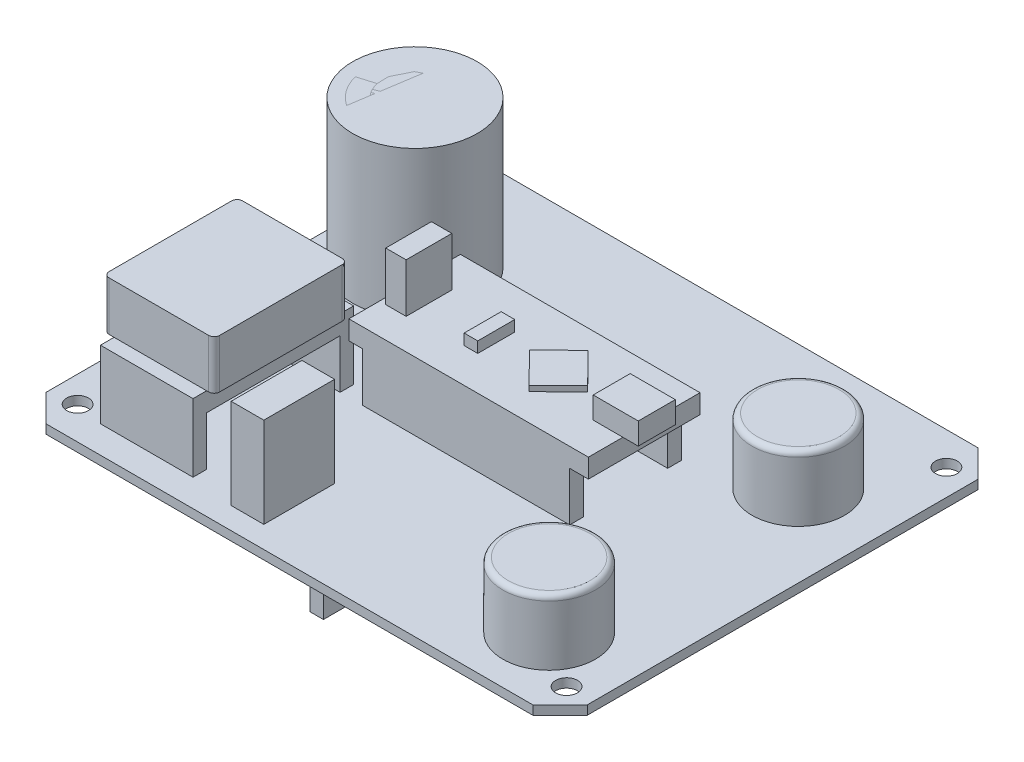
SolidWorks part; units mm, degrees
ref_plane "前视基准面" through (0, 0, 0) normal (0, 0, 1) x (1, 0, 0)
ref_plane "上视基准面" through (0, 0, 0) normal (0, 1, 0) x (1, 0, 0)
ref_plane "右视基准面" through (0, 0, 0) normal (1, 0, 0) x (0, 0, -1)
sketch "草图1" plane through (0, 0, 0) normal (0, 1, 0) x (1, 0, 0)
  line L0 (-49.7, 35.88) -> (-44.7, 40.88)
  line L1 (-44.7, 40.88) -> (44.7, 40.88)
  line L2 (-49.7, 35.88) -> (-49.7, -35.88)
  line L3 (-44.7, -40.88) -> (44.7, -40.88)
  line L4 (49.7, 35.88) -> (49.7, -35.88)
  line L5 (-49.7, 40.88) -> (-46.9566, 38.6234) construction
  line L6 (-49.7, -40.88) -> (-46.9566, -38.6234) construction
  line L7 (44.7, 40.88) -> (49.7, 35.88)
  line L8 (44.7, -40.88) -> (49.7, -35.88)
  line L9 (-49.7, -35.88) -> (-44.7, -40.88)
  line L10 (46.9566, 38.6234) -> (49.7, 40.88) construction
  line L11 (46.9566, -38.6234) -> (49.7, -40.88) construction
  line L12 (0, 0) -> (0, 46.3882) construction
  line L13 (0, 0) -> (77.8977, 0) construction
  line L14 (-39.7, -6.38) -> (-22.7, -6.38)
  line L15 (-39.7, -33.38) -> (-22.7, -33.38)
  line L16 (-39.7, -33.38) -> (-39.7, -35.88)
  line L17 (-39.7, -35.88) -> (-22.7, -35.88)
  line L18 (-22.7, -33.38) -> (-22.7, -35.88)
  line L19 (-39.7, -8.88) -> (-22.7, -8.88)
  line L20 (-39.7, -6.38) -> (-39.7, -8.88)
  line L21 (-22.7, -6.38) -> (-22.7, -8.88)
  line L22 (-18.5299, 11.62) -> (19.4701, 11.62)
  line L23 (-14.7, -23.88) -> (-8.7, -23.88)
  line L24 (-14.7, -23.88) -> (-14.7, -36.88)
  line L25 (-14.7, -36.88) -> (-8.7, -36.88)
  line L26 (-8.7, -23.88) -> (-8.7, -36.88)
  line L27 (-18.5299, -6.38) -> (19.4701, -6.38)
  line L28 (-18.5299, -6.38) -> (-18.5299, -8.88)
  line L29 (-18.5299, -8.88) -> (19.4701, -8.88)
  line L30 (19.4701, -6.38) -> (19.4701, -8.88)
  line L31 (-18.5299, 9.12) -> (19.4701, 9.12)
  line L32 (-18.5299, 11.62) -> (-18.5299, 9.12)
  line L33 (19.4701, 11.62) -> (19.4701, 9.12)
  circle A0 centre (-44.9, 34.88) radius 2
  circle A1 centre (44.9, 34.88) radius 2
  circle A2 centre (44.9, -34.88) radius 2
  circle A3 centre (-44.9, -34.88) radius 2
  circle A4 centre (-35.7, 17.88) radius 11.44
  circle A5 centre (34.7, 17.88) radius 8.5
  circle A6 centre (34.7, -27.88) radius 8.5
  point P0 (0, 0)
  dimension "D11" = 4
  dimension "D12" = 6
  dimension "D13" = 4.8
  dimension "D14" = 22.88
  dimension "D15" = 14
  dimension "D16" = 23
  dimension "D17" = 15
  dimension "D18" = 13
  dimension "D1" = 81.76
  dimension "D2" = 99.4
  dimension "D3" = 5
  dimension "D4" = 45
  dimension "D5" = 5
  dimension "D6" = 45
  dimension "D7" = 5
  dimension "D8" = 45
  dimension "D9" = 5
  dimension "D10" = 45
  dimension "D19" = 17
  dimension "D20" = 2.5
  dimension "D22" = 6
  dimension "D23" = 13
  dimension "D24" = 4
  dimension "D25" = 8
  dimension "D26" = 10
  dimension "D27" = 5
  dimension "D28" = 38
  dimension "D21" = 2
  dimension "D29" = 2
extrude "凸台-拉伸1" add sketch "草图1" against normal blind 1.66 contours A0 | L2 L9 L3 L8 L4 L7 L1 L0 | A1 | A3 | A2 region at (-44.9, 0, -34.88)
extrude "凸台-拉伸2" add sketch "草图1<3>" along normal blind 9 contours L30 L27 L28 L29 | L18 L15 L16 L17 | L31 L33 L22 L32 | L14 L21 L19 L20 region at (-31.2, 0, 34.63) region at (0.4701, 0, 7.63)
sketch "草图1<3>" plane through (0, 0, 0) normal (0, 1, 0) x (1, 0, 0) same geometry as "草图1"
extrude "凸台-拉伸3" add sketch "草图1<4>" along normal blind 16.58 contours L23 L26 L25 L24
sketch "草图1<4>" plane through (0, 0, 0) normal (0, 1, 0) x (1, 0, 0) same geometry as "草图1"
sketch "草图2" plane through (0, 0, 0) normal (0, 1, 0) x (1, 0, 0)
  circle A0 centre (-35.7, 17.88) radius 9.0479
  circle A1 centre (-35.7, 17.88) radius 5.836
extrude "凸台-拉伸4" add sketch "草图2" along normal blind 27 contours A1 | A0 region at (-35.7, 0, -17.88)
extrude "凸台-拉伸6" add sketch "草图2<4>" along normal blind 27 separate body contours A1
sketch "草图2<4>" plane through (0, 0, 0) normal (0, 1, 0) x (1, 0, 0) same geometry as "草图2"
extrude "凸台-拉伸7" add sketch "草图1<5>" along normal blind 27 separate body contours A4
sketch "草图1<5>" plane through (0, 0, 0) normal (0, 1, 0) x (1, 0, 0) same geometry as "草图1"
extrude "凸台-拉伸8" add sketch "草图1<6>" along normal blind 12 contours A5
sketch "草图1<6>" plane through (0, 0, 0) normal (0, 1, 0) x (1, 0, 0) same geometry as "草图1"
fillet "圆角1" radius 1 1 edges at (34.7, 12, -9.38)
extrude "凸台-拉伸9" add sketch "草图1<7>" along normal blind 12 contours A6
sketch "草图1<7>" plane through (0, 0, 0) normal (0, 1, 0) x (1, 0, 0) same geometry as "草图1"
fillet "圆角2" radius 1 1 edges at (34.7, 12, 36.38)
sketch "草图4" plane through (0, -1.66, 0) normal (0, -1, 0) x (1, 0, 0)
  line L0 (0, 43.8226) -> (0, -47.1107) construction
  line L1 (-44.7, 40.88) -> (44.7, 40.88) construction
  line L2 (-16, 19.88) -> (16, 19.88)
  line L3 (-16, 19.88) -> (-16, 17.38)
  line L4 (-16, 17.38) -> (16, 17.38)
  line L5 (16, 19.88) -> (16, 17.38)
  line L6 (-16, 19.88) -> (16, 17.38) construction
  line L7 (-16, 17.38) -> (16, 19.88) construction
  line L8 (-16, -21.12) -> (16, -21.12)
  line L9 (-16, -18.62) -> (16, -18.62)
  line L10 (-16, -18.62) -> (-16, -21.12)
  line L11 (16, -18.62) -> (16, -21.12)
  line L12 (-44.7, -40.88) -> (44.7, -40.88) construction
  line L13 (-1.25, 35.88) -> (1.25, 35.88)
  line L14 (-1.25, 35.88) -> (-1.25, 21.88)
  line L15 (-1.25, 21.88) -> (1.25, 21.88)
  line L16 (1.25, 35.88) -> (1.25, 21.88)
  line L17 (-1.25, 35.88) -> (1.25, 21.88) construction
  line L18 (-1.25, 21.88) -> (1.25, 35.88) construction
  line L19 (-27, -25.88) -> (-18, -25.88)
  line L20 (-27, -25.88) -> (-27, -37.88)
  line L21 (-27, -37.88) -> (-18, -37.88)
  line L22 (-18, -25.88) -> (-18, -37.88)
  line L23 (-27, -25.88) -> (-18, -37.88) construction
  line L24 (-27, -37.88) -> (-18, -25.88) construction
  line L25 (-27, -23.88) -> (-18, -23.88)
  line L26 (-27, -23.88) -> (-27, -25.88)
  line L27 (-27, -25.88) -> (-18, -25.88)
  line L28 (-18, -23.88) -> (-18, -25.88)
  line L29 (-27, -23.88) -> (-18, -25.88) construction
  line L30 (-27, -25.88) -> (-18, -23.88) construction
  line L31 (27, -25.88) -> (18, -25.88)
  line L32 (18, -23.88) -> (18, -25.88)
  line L33 (27, -23.88) -> (18, -23.88)
  line L34 (27, -23.88) -> (27, -25.88)
  line L35 (27, -37.88) -> (18, -37.88)
  line L36 (18, -25.88) -> (18, -37.88)
  line L37 (27, -25.88) -> (18, -25.88)
  line L38 (27, -25.88) -> (27, -37.88)
  point P3 (0, 18.63)
  point P11 (0, 28.88)
  point P19 (-22.5, -31.88)
  point P24 (-22.5, -24.88)
  point P29 (-16, -19.87)
  point P36 (0, 0)
  dimension "D1" = 2.5
  dimension "D2" = 32
  dimension "D3" = 21
  dimension "D5" = 2.5
  dimension "D6" = 14
  dimension "D7" = 5
  dimension "D8" = 9
  dimension "D9" = 3
  dimension "D10" = 2
  dimension "D11" = 12
  dimension "D12" = 2
  dimension "D4" = 2
extrude "凸台-拉伸10" add sketch "草图4" along normal blind 9 contours L16 L13 L14 L15 | L9 L11 L8 L10 | L4 L5 L2 L3 region at (0, -1.66, 28.88)
extrude "凸台-拉伸11" add sketch "草图4<5>" along normal blind 11 contours L22 L19 L20 L21 | L38 L31 L36 L35 region at (-22.5, -1.66, -31.88) region at (22.5, -1.66, -31.88)
sketch "草图4<5>" plane through (0, -1.66, 0) normal (0, -1, 0) x (1, 0, 0) same geometry as "草图4"
fillet "圆角4" radius 4.5 4 edges at (27, -12.66, -31.88) (18, -12.66, -31.88) (-18, -12.66, -31.88) (-27, -12.66, -31.88)
extrude "凸台-拉伸12" add sketch "草图4<6>" along normal blind 11 separate body contours L28 L25 L26 L19 | L34 L33 L32 L31 region at (-22.5, -1.66, -24.88) region at (22.5, -1.66, -24.88)
sketch "草图4<6>" plane through (0, -1.66, 0) normal (0, -1, 0) x (1, 0, 0) same geometry as "草图4"
sketch "草图5" plane through (0, 0, -23.88) normal (0, 0, 1) x (1, 0, 0)
  circle A0 centre (-22.5, -7.16) radius 3
  circle A1 centre (22.5, -7.16) radius 3
extrude "切除-拉伸1" cut sketch "草图5" against normal blind 11
sketch "草图6" plane through (0, 0, -34.88) normal (0, 0, 1) x (1, 0, 0)
  circle A0 centre (-22.5, -7.16) radius 1
  circle A1 centre (22.5, -7.16) radius 1
extrude "凸台-拉伸13" add sketch "草图6" along normal blind 8
sketch "草图7" plane through (0, 9, 0) normal (0, 1, 0) x (1, 0, 0)
  line L1 (-21.0893, 11.62) -> (22.9107, 11.62)
  line L2 (-21.0893, 11.62) -> (-21.0893, -8.88)
  line L3 (-21.0893, -8.88) -> (22.9107, -8.88)
  line L4 (22.9107, 11.62) -> (22.9107, -8.88)
  line L5 (-39.7, -6.38) -> (-22.7, -6.38)
  line L6 (-39.7, -6.38) -> (-39.7, -35.88)
  line L7 (-39.7, -35.88) -> (-22.7, -35.88)
  line L8 (-22.7, -6.38) -> (-22.7, -35.88)
  dimension "D1" = 44
extrude "凸台-拉伸14" add sketch "草图7" along normal blind 3.5
sketch "草图8" plane through (0, 12.5, 0) normal (0, 1, 0) x (1, 0, 0)
  line L0 (1.474, 1.7574) -> (6.9164, 7.0865)
  line L1 (1.474, 1.7574) -> (7.0356, -3.9225)
  line L2 (6.9164, 7.0865) -> (12.478, 1.4065)
  line L3 (7.0356, -3.9225) -> (12.478, 1.4065)
  line L5 (17.461, 4.2465) -> (25.738, 4.2465)
  line L6 (17.461, 4.2465) -> (17.461, -2.5511)
  line L7 (17.461, -2.5511) -> (25.738, -2.5511)
  line L8 (25.738, 4.2465) -> (25.738, -2.5511)
  line L9 (-19.9554, 5.1589) -> (-16.2138, 5.1589)
  line L10 (-19.9554, 5.1589) -> (-19.9554, -3.2314)
  line L11 (-19.9554, -3.2314) -> (-16.2138, -3.2314)
  line L12 (-16.2138, 5.1589) -> (-16.2138, -3.2314)
  line L13 (-6.2361, 4.2465) -> (-3.7416, 4.2465)
  line L14 (-6.2361, 4.2465) -> (-6.2361, -2.5511)
  line L15 (-6.2361, -2.5511) -> (-3.7416, -2.5511)
  line L16 (-3.7416, 4.2465) -> (-3.7416, -2.5511)
extrude "凸台-拉伸15" add sketch "草图8" along normal blind 1 contours L1 L3 L2 L0 region at (6.976, 12.5, -1.582)
extrude "凸台-拉伸16" add sketch "草图8<3>" along normal blind 4 separate body contours L7 L8 L5 L6
sketch "草图8<3>" plane through (0, 12.5, 0) normal (0, 1, 0) x (1, 0, 0) same geometry as "草图8"
extrude "凸台-拉伸17" add sketch "草图8<4>" along normal blind 9 separate body contours L12 L11 L10 L9
sketch "草图8<4>" plane through (0, 12.5, 0) normal (0, 1, 0) x (1, 0, 0) same geometry as "草图8"
extrude "凸台-拉伸18" add sketch "草图8<5>" along normal blind 2 contours L15 L16 L13 L14
sketch "草图8<5>" plane through (0, 12.5, 0) normal (0, 1, 0) x (1, 0, 0) same geometry as "草图8"
sketch "草图9" plane through (0, 12.5, 0) normal (0, 1, 0) x (1, 0, 0)
  line L1 (-41.6116, -8.88) -> (-21.316, -8.88)
  line L2 (-41.6116, -8.88) -> (-41.6116, -33.38)
  line L3 (-41.6116, -33.38) -> (-21.316, -33.38)
  line L4 (-21.316, -8.88) -> (-21.316, -33.38)
extrude "凸台-拉伸19" add sketch "草图9" along normal blind 9 separate body
sketch "草图10" plane through (0, -10.66, 0) normal (0, -1, 0) x (-1, 0, 0)
  line L1 (20.5706, -19.88) -> (-21.4294, -19.88)
  line L2 (20.5706, -19.88) -> (20.5706, 21.12)
  line L3 (20.5706, 21.12) -> (-21.4294, 21.12)
  line L4 (-21.4294, -19.88) -> (-21.4294, 21.12)
  dimension "D1" = 42
  dimension "D2" = 41
extrude "凸台-拉伸20" add sketch "草图10" along normal blind 1.8
sketch "草图11" plane through (0, -12.46, 0) normal (0, -1, 0) x (1, 0, 0)
  line L1 (-13.7194, 9.5809) -> (11.5651, 9.5809)
  line L2 (-13.7194, 9.5809) -> (-13.7194, -15.3634)
  line L3 (-13.7194, -15.3634) -> (11.5651, -15.3634)
  line L4 (11.5651, 9.5809) -> (11.5651, -15.3634)
extrude "凸台-拉伸21" add sketch "草图11" along normal blind 1.8
sketch "草图12" plane through (0, -12.46, 0) normal (0, -1, 0) x (-1, 0, 0)
  circle A0 centre (-18.0279, 17.1776) radius 1
extrude "凸台-拉伸22" add sketch "草图12" along normal blind 1
fillet "圆角5" radius 1 4 edges at (-21.316, 17, 8.88) (-41.6116, 17, 8.88) (-21.316, 17, 33.38) (-41.6116, 17, 33.38)
